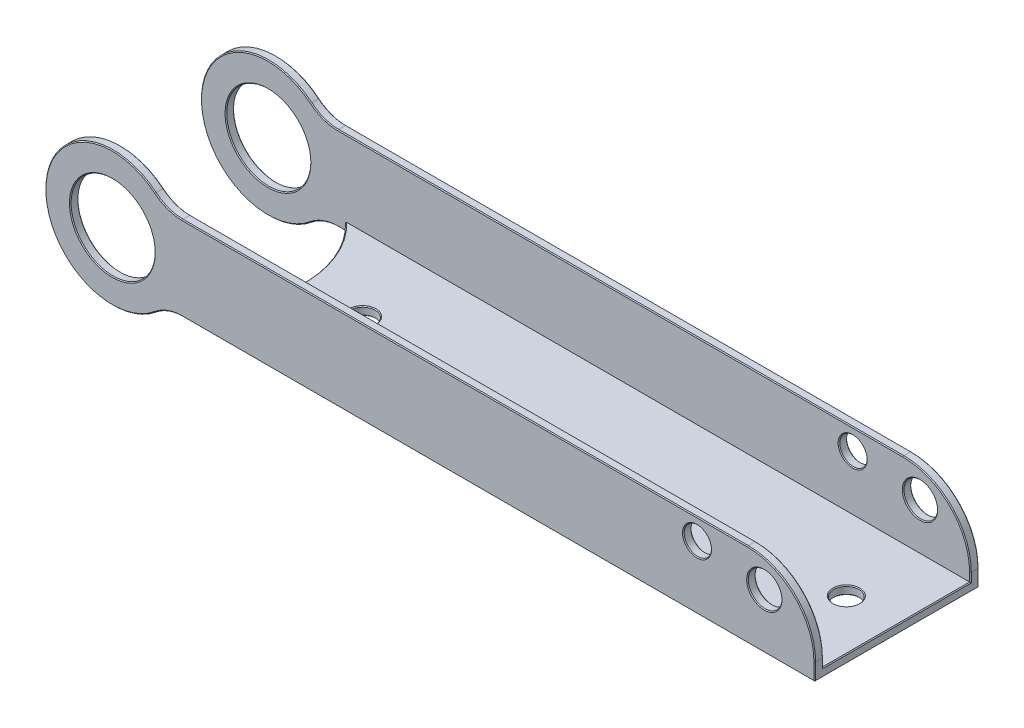
SolidWorks part; units mm, degrees
ref_plane "正面" through (0, 0, 0) normal (0, 0, 1) x (1, 0, 0)
ref_plane "平面" through (0, 0, 0) normal (0, 1, 0) x (1, 0, 0)
ref_plane "右側面" through (0, 0, 0) normal (1, 0, 0) x (0, 0, -1)
sketch "ｽｹｯﾁ1" plane through (0, 0, 0) normal (0, 0, 1) x (1, 0, 0)
  line L0 (12.49, 10) -> (12.49, -10) construction
  line L1 (12.49, 10) -> (167, 10)
  line L3 (12.49, -10) -> (167, -10)
  line L4 (167, 10) -> (167, -10)
  arc A0 (12.49, 10) -> (12.49, -10) centre (0, 0) ccw
  dimension "D1" = 32
  dimension "D2" = 167
  dimension "D3" = 10
extrude "ﾎﾞｽ - 押し出し1" add sketch "ｽｹｯﾁ1" along normal mid plane 39
fillet "ﾌｨﾚｯﾄ1" radius 16 1 edges at (167, 10, 0)
fillet "ﾌｨﾚｯﾄ2" radius 10 2 edges at (12.49, -10, 0) (12.49, 10, 0)
sketch "ｽｹｯﾁ2" plane through (0, 0, 0) normal (0, 0, 1) x (1, 0, 0)
  circle A0 centre (0, 0) radius 10
  dimension "D1" = 20
extrude "ｶｯﾄ - 押し出し1" cut sketch "ｽｹｯﾁ2" against normal through all both and the other way through all
sketch "ｽｹｯﾁ3" plane through (0, 0, 0) normal (0, 1, 0) x (1, 0, 0)
  line L0 (-16, 19.5) -> (-16, -19.5) construction
  line L1 (-16, 17.5) -> (18.4241, 17.5)
  line L2 (-16, 17.5) -> (-16, -17.5)
  line L3 (-16, -17.5) -> (18.4241, -17.5)
  line L5 (-16, -19.5) -> (10.2235, -19.5) construction
  line L7 (10.2235, 19.5) -> (-16, 19.5) construction
  arc A0 (18.4241, 17.5) -> (18.4241, -17.5) centre (2, 0) cw
  dimension "D1" = 24
  dimension "D2" = 2
  dimension "D3" = 2
  dimension "D4" = 18
extrude "ｶｯﾄ - 押し出し2" cut sketch "ｽｹｯﾁ3" against normal through all both and the other way through all
sketch "ｽｹｯﾁ4" plane through (0, 0, 0) normal (1, 0, 0) x (0, 0, -1)
  line L0 (-19.5, 10) -> (19.5, 10) construction
  line L1 (-17.5, -8) -> (17.5, -8)
  line L2 (-17.5, -8) -> (-17.5, 10)
  line L3 (-17.5, 10) -> (17.5, 10)
  line L4 (17.5, -8) -> (17.5, 10)
  line L7 (17.5, 16) -> (17.5, -16) construction
  line L8 (-17.5, -16) -> (-17.5, 16) construction
  line L9 (-19.5, -10) -> (19.5, -10) construction
  dimension "D1" = 2
extrude "ｶｯﾄ - 押し出し3" cut sketch "ｽｹｯﾁ4" along normal through all
sketch "ｽｹｯﾁ5" plane through (0, 0, 19.5) normal (0, 0, 1) x (1, 0, 0)
  line L0 (167, -10) -> (167, -6) construction
  line L1 (16.6132, -10) -> (167, -10) construction
  circle A0 centre (155, 3) radius 4
  circle A1 centre (139, 5) radius 3.25
  dimension "D1" = 12
  dimension "D2" = 28
  dimension "D4" = 15
  dimension "D5" = 8
  dimension "D6" = 6.5
  dimension "D3" = 13
extrude "ｶｯﾄ - 押し出し4" cut sketch "ｽｹｯﾁ5" against normal through all
sketch "ｽｹｯﾁ6" plane through (0, -10, 0) normal (0, -1, 0) x (1, 0, 0)
  line L0 (167, 19.5) -> (167, -19.5) construction
  circle A0 centre (155, 0) radius 3
  circle A1 centre (40, 0) radius 3
  dimension "D1" = 12
  dimension "D3" = 6
  dimension "D4" = 6
  dimension "D2" = 127
extrude "ｶｯﾄ - 押し出し5" cut sketch "ｽｹｯﾁ6" against normal through all
chamfer "面取り1" distance 0.2 angle 45 48 edges at (142.25, 5, 19.5) (142.25, 5, 17.5) (159, 3, 19.5) (159, 3, 17.5) (135.75, 5, -17.5) (142.25, 5, -19.5) (151, 3, -17.5) (159, 3, -19.5) (10, 0, 19.5) (10, 0, 17.5) (-10, 0, -17.5) (10, 0, -19.5) (17.5187, -10, -17.5) (13.2164, -10.5946, -17.5) (-16, 0, -17.5) (13.2164, 10.5946, -17.5) (83.8066, 10, -17.5) (167, -7, -17.5) (162.3137, 5.3137, -17.5) (17.5187, -10, 17.5) (13.2164, -10.5946, 17.5) (-16, 0, 17.5) (13.2164, 10.5946, 17.5) (167, -7, 17.5) (83.8066, 10, 17.5) (162.3137, 5.3137, 17.5) (167, -8, 0) (167, -8, 19.5) (167, -8, -19.5) (162.3137, 5.3137, 19.5) (162.3137, 5.3137, -19.5) (83.8066, 10, 19.5) (83.8066, 10, -19.5) (13.2164, 10.5946, 19.5) (13.2164, 10.5946, -19.5) (-16, 0, 19.5) (-16, 0, -19.5) (13.2164, -10.5946, 19.5) (13.2164, -10.5946, -19.5) (91.8066, -10, 19.5) (167, -10, 0) (91.8066, -10, -19.5) (155, -10, -3) (155, -8, 3) (40, -10, -3) (40, -8, 3) (26, -10, 0) (26, -8, 0)
